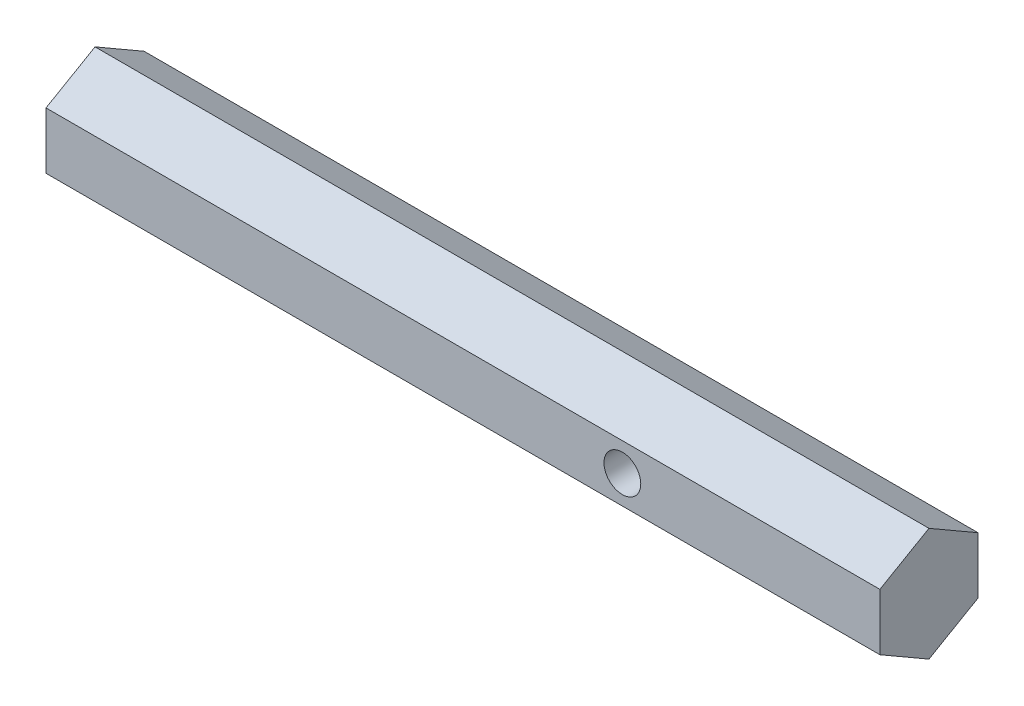
SolidWorks part; units mm, degrees
ref_plane "Front" through (0, 0, 0) normal (0, 0, 1) x (1, 0, 0)
ref_plane "Top" through (0, 0, 0) normal (0, 1, 0) x (1, 0, 0)
ref_plane "Right" through (0, 0, 0) normal (1, 0, 0) x (0, 0, -1)
sketch "Sketch1" plane through (0, 0, 0) normal (1, 0, 0) x (0, 0, -1)
  line L1 (6.35, -3.6662) -> (6.35, 3.6662)
  line L2 (6.35, 3.6662) -> (0, 7.3323)
  line L3 (0, 7.3323) -> (-6.35, 3.6662)
  line L4 (-6.35, 3.6662) -> (-6.35, -3.6662)
  line L5 (-6.35, -3.6662) -> (0, -7.3323)
  line L6 (0, -7.3323) -> (6.35, -3.6662)
  circle A0 centre (0, 0) radius 6.35 construction
  dimension "D1" = 12.7
extrude "Boss-Extrude1" add sketch "Sketch1" along normal blind 107.95
sketch "Sketch2" plane through (0, 0, 6.35) normal (0, 0, 1) x (1, 0, 0)
  line L0 (0, 3.6662) -> (0, -3.6662) construction
  circle A0 centre (74.6125, 0) radius 2.3813
  dimension "D2" = 4.7625
  dimension "D1" = 74.6125
extrude "Cut-Extrude1" cut sketch "Sketch2" against normal through all
